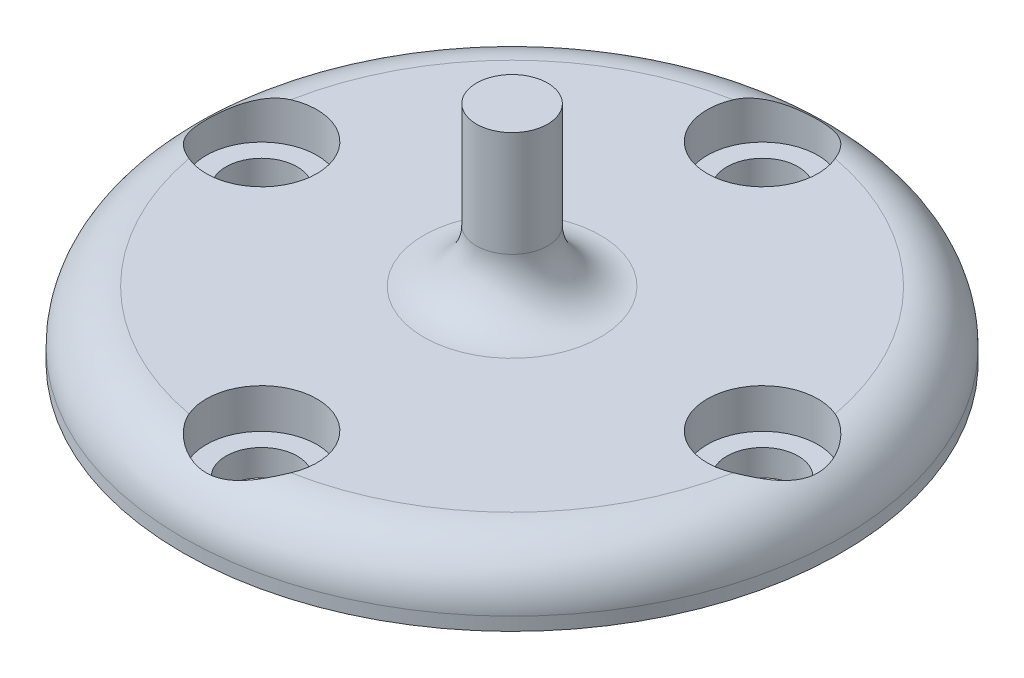
SolidWorks part; units mm, degrees
ref_plane "Front Plane" through (0, 0, 0) normal (0, 0, 1) x (1, 0, 0)
ref_plane "Top Plane" through (0, 0, 0) normal (0, 1, 0) x (1, 0, 0)
ref_plane "Right Plane" through (0, 0, 0) normal (1, 0, 0) x (0, 0, -1)
sketch "Sketch1" plane through (0, 0, 0) normal (0, 1, 0) x (1, 0, 0)
  circle A0 centre (0, 0) radius 12.5
  dimension "D1" = 25
extrude "Boss-Extrude1" add sketch "Sketch1" along normal blind 2.5
sketch "Sketch2" plane through (0, 2.5, 0) normal (0, 1, 0) x (1, 0, 0)
  circle A0 centre (0, 0) radius 9.5 construction
  circle A1 centre (0, 9.5) radius 1.35
  dimension "D1" = 19
  dimension "D2" = 2.7
extrude "Cut-Extrude1" cut sketch "Sketch2" against normal through all
sketch "Sketch4" plane through (0, 2.5, 0) normal (0, 1, 0) x (1, 0, 0)
  circle A0 centre (0, 9.5) radius 2.1
  dimension "D1" = 4.2
extrude "Cut-Extrude2" cut sketch "Sketch4" against normal blind 1.5
pattern_circular "CirPattern1" count 4 over 360 about axis through (0, 2.5, 0) along (0, -1, 0) of "Cut-Extrude1", "Cut-Extrude2"
sketch "Sketch3" plane through (0, 2.5, 0) normal (0, 1, 0) x (1, 0, 0)
  circle A0 centre (0, 0) radius 1.35
  dimension "D1" = 2.7
extrude "Boss-Extrude2" add sketch "Sketch3" along normal blind 6
fillet "Fillet2" radius 2 1 edges at (0, 2.5, 1.35)
fillet "Fillet3" radius 2 1 edges at (0, 2.5, 12.5)
